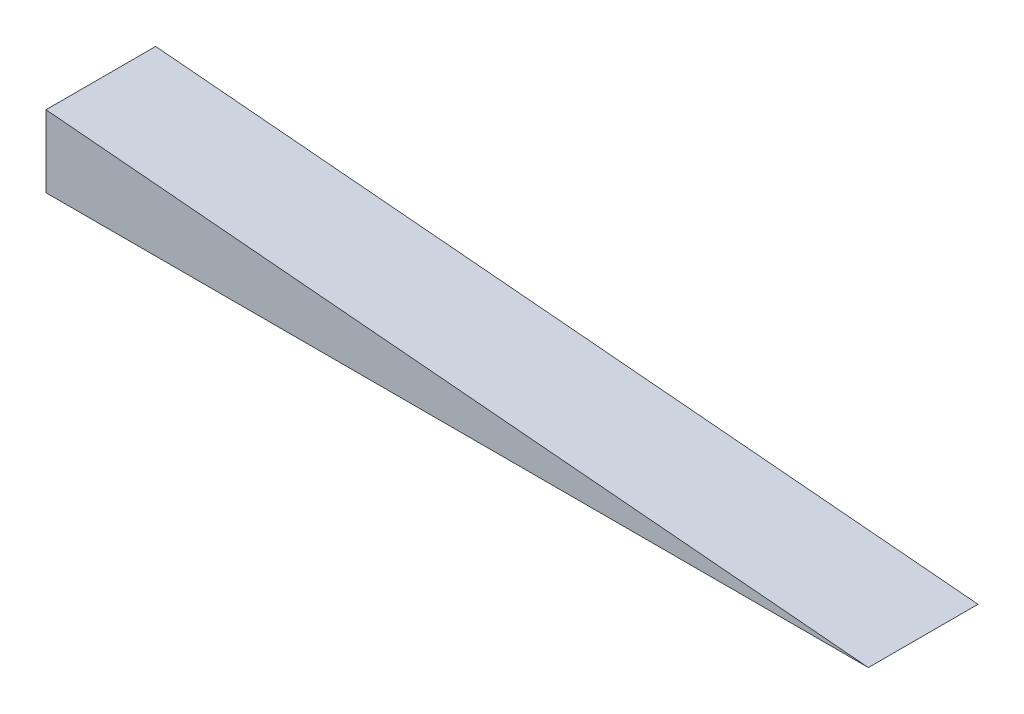
SolidWorks part; units mm, degrees
ref_plane "Front Plane" through (0, 0, 0) normal (0, 0, 1) x (1, 0, 0)
ref_plane "Top Plane" through (0, 0, 0) normal (0, 1, 0) x (1, 0, 0)
ref_plane "Right Plane" through (0, 0, 0) normal (1, 0, 0) x (0, 0, -1)
sketch "Sketch1" plane through (0, 0, 0) normal (0, 0, 1) x (1, 0, 0)
  line L0 (-49.0278, 0) -> (100.9722, 0)
  line L1 (55, 0) -> (-55, 0) construction
  line L2 (100.9722, 0) -> (-49.0278, 13.1233)
  line L3 (-49.0278, 13.1233) -> (-49.0278, 0)
  dimension "D1" = 150
  dimension "D2" = 5
extrude "Boss-Extrude1" add sketch "Sketch1" along normal mid plane 20
